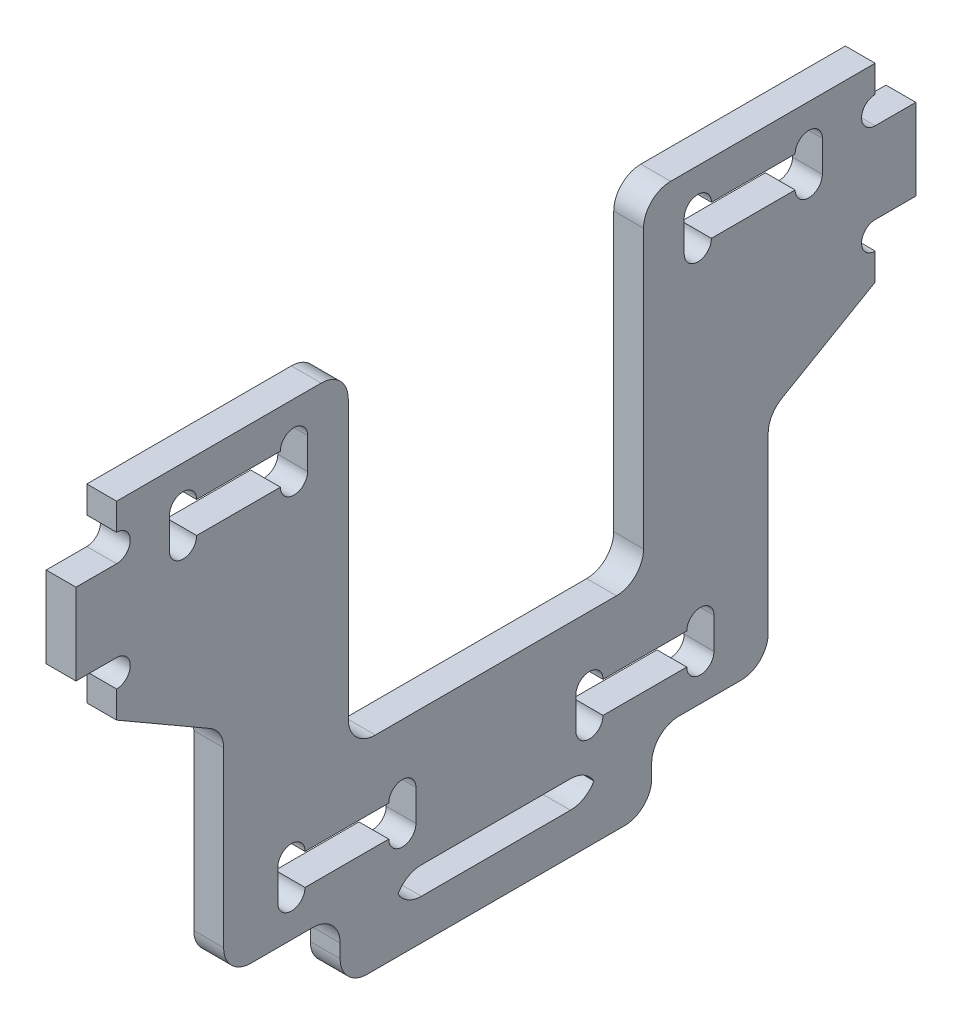
SolidWorks part; units mm, degrees
material "Thornel Mat VMA"
ref_plane "前视基准面" through (0, 0, 0) normal (0, 0, 1) x (1, 0, 0)
ref_plane "上视基准面" through (0, 0, 0) normal (0, 1, 0) x (1, 0, 0)
ref_plane "右视基准面" through (0, 0, 0) normal (1, 0, 0) x (0, 0, -1)
sketch "草图1" plane through (0, 0, 0) normal (1, 0, 0) x (0, 0, -1)
  line L0 (0, 0) -> (0, 15.6623) construction
  line L1 (28, -17.25) -> (-28, -17.25) construction
  line L3 (28, 17.25) -> (10.9, 17.25)
  line L5 (28, -17.25) -> (-28, 17.25) construction
  line L6 (28, 17.25) -> (-28, -17.25) construction
  line L7 (-13.9, 12.1) -> (-24.1, 12.1)
  line L8 (-13.9, 12.1) -> (-13.9, 14.4)
  line L9 (-13.9, 14.4) -> (-24.1, 14.4)
  line L10 (-24.1, 12.1) -> (-24.1, 14.4)
  line L11 (-13.9, 12.1) -> (-24.1, 14.4) construction
  line L12 (-13.9, 14.4) -> (-24.1, 12.1) construction
  line L13 (13.9, 14.4) -> (24.1, 14.4)
  line L14 (24.1, 12.1) -> (24.1, 14.4)
  line L15 (13.9, 12.1) -> (24.1, 12.1)
  line L16 (13.9, 12.1) -> (13.9, 14.4)
  line L17 (19, 14.4) -> (19, 10.7005) construction
  line L18 (0, 0) -> (11.4572, 0) construction
  line L27 (5.9, -12.1) -> (16.1, -14.4) construction
  line L28 (-10.9, 17.25) -> (-10.9, -7.25)
  line L29 (-10.9, -7.25) -> (10.9, -7.25)
  line L30 (10.9, -7.25) -> (10.9, 17.25)
  line L31 (-10.9, 17.25) -> (-28, 17.25)
  line L32 (-28, 13.25) -> (-31, 13.25)
  line L33 (-31, 13.25) -> (-31, 7.25)
  line L34 (-31, 7.25) -> (-28, 7.25)
  line L35 (-31, 10.25) -> (-27.1728, 10.25) construction
  line L36 (-28, 13.25) -> (-28, 17.25)
  line L37 (31, 7.25) -> (28, 7.25)
  line L38 (31, 13.25) -> (31, 7.25)
  line L39 (28, 13.25) -> (31, 13.25)
  line L40 (28, 13.25) -> (28, 17.25)
  line L41 (-28, 3.25) -> (-20.1, -1.3111)
  line L42 (-20.1, -1.3111) -> (-20.1, -17.25)
  line L44 (-28, 3.25) -> (-28, 7.25)
  line L46 (20.1, -1.3111) -> (20.1, -17.25)
  line L47 (28, 3.25) -> (20.1, -1.3111)
  line L48 (28, 3.25) -> (28, 7.25)
  line L49 (-5.9, -14.4) -> (-16.1, -14.4)
  line L50 (-5.9, -14.4) -> (-5.9, -12.1)
  line L51 (-5.9, -12.1) -> (-16.1, -12.1)
  line L52 (-16.1, -14.4) -> (-16.1, -12.1)
  line L53 (-5.9, -14.4) -> (-16.1, -12.1) construction
  line L54 (-5.9, -12.1) -> (-16.1, -14.4) construction
  line L55 (5.9, -14.4) -> (16.1, -12.1) construction
  line L56 (16.1, -14.4) -> (16.1, -12.1)
  line L57 (5.9, -12.1) -> (16.1, -12.1)
  line L58 (5.9, -14.4) -> (5.9, -12.1)
  line L59 (5.9, -14.4) -> (16.1, -14.4)
  line L60 (-20.1, -17.25) -> (20.1, -17.25)
  circle A0 centre (-23.095, 14.4) radius 1.005
  circle A1 centre (-14.905, 14.4) radius 1.005
  circle A2 centre (-23.095, 12.1) radius 1.005
  circle A3 centre (-14.905, 12.1) radius 1.005
  circle A4 centre (14.905, 12.1) radius 1.005
  circle A5 centre (23.095, 12.1) radius 1.005
  circle A6 centre (23.095, 14.4) radius 1.005
  circle A7 centre (14.905, 14.4) radius 1.005
  circle A16 centre (-28, 14.255) radius 1.005
  circle A17 centre (-28, 6.245) radius 1.005
  circle A18 centre (28, 6.245) radius 1.005
  circle A19 centre (28, 14.255) radius 1.005
  circle A20 centre (-6.905, -12.1) radius 1.005
  circle A21 centre (-6.905, -14.4) radius 1.005
  circle A22 centre (-15.095, -14.4) radius 1.005
  circle A23 centre (-15.095, -12.1) radius 1.005
  circle A24 centre (15.095, -12.1) radius 1.005
  circle A25 centre (15.095, -14.4) radius 1.005
  circle A26 centre (6.905, -14.4) radius 1.005
  circle A27 centre (6.905, -12.1) radius 1.005
  point P0 (0, 0)
  point P6 (-19, 13.25)
  point P19 (-11, -13.25)
  point P61 (11, -13.25)
  dimension "D7" = 2.01
  dimension "D1" = 2.3
  dimension "D2" = 10.2
  dimension "D3" = 38
  dimension "D4" = 4
  dimension "D5" = 10.2
  dimension "D6" = 26.5
  dimension "D8" = 10
  dimension "D9" = 56
  dimension "D10" = 3
  dimension "D11" = 3
  dimension "D12" = 6
  dimension "D13" = 7
  dimension "D15" = 4
  dimension "D16" = 2.3
  dimension "D17" = 7
  dimension "D18" = 22
  dimension "D19" = 4
  dimension "D20" = 60
extrude "凸台-拉伸1" add sketch "草图1" along normal blind 2.2 contours L28 L31 L1 L3 L30 L29 A3 L7 A2 L10 A0 L9 A1 L8 L16 A7 L13 A6 L14 A5 L15 A4 L50 region at (0, 16.255, -27.2905)
sketch "草图2" plane through (2.2, 0, 0) normal (1, 0, 0) x (0, 0, -1)
  line L0 (-11.5, -17.25) -> (-11.5, -22.25)
  line L1 (-20.1, -17.25) -> (20.1, -17.25) construction
  line L2 (-11.5, -22.25) -> (11.5, -22.25)
  line L3 (11.5, -22.25) -> (11.5, -17.25)
  line L4 (-7.5, -17.25) -> (-7.5, -19.26)
  line L5 (-7.5, -19.26) -> (7.5, -19.26)
  line L6 (7.5, -19.26) -> (7.5, -17.25)
  line L7 (0, 0) -> (0, -10.5808) construction
  line L8 (-11.5, -17.25) -> (-7.5, -17.25)
  line L9 (7.5, -17.25) -> (11.5, -17.25)
  dimension "D1" = 2.01
  dimension "D2" = 5
  dimension "D3" = 4
  dimension "D4" = 15
extrude "凸台-拉伸2" add sketch "草图2" against normal up to surface (2.2 mm away) up to face at (0, -13.25, 11)
fillet "圆角1" radius 2 16 edges at (1.1, -17.25, 20.1) (1.1, -17.25, -20.1) (1.1, -1.3111, -20.1) (1.1, 17.25, -10.9) (1.1, -7.25, -10.9) (1.1, -7.25, 10.9) (1.1, 17.25, 10.9) (1.1, -1.3111, 20.1) (1.1, -19.26, -7.5) (1.1, -19.26, 7.5) (1.1, -17.25, 7.5) (1.1, -17.25, -7.5) (1.1, -17.25, -11.5) (1.1, -22.25, -11.5) (1.1, -22.25, 11.5) (1.1, -17.25, 11.5)
